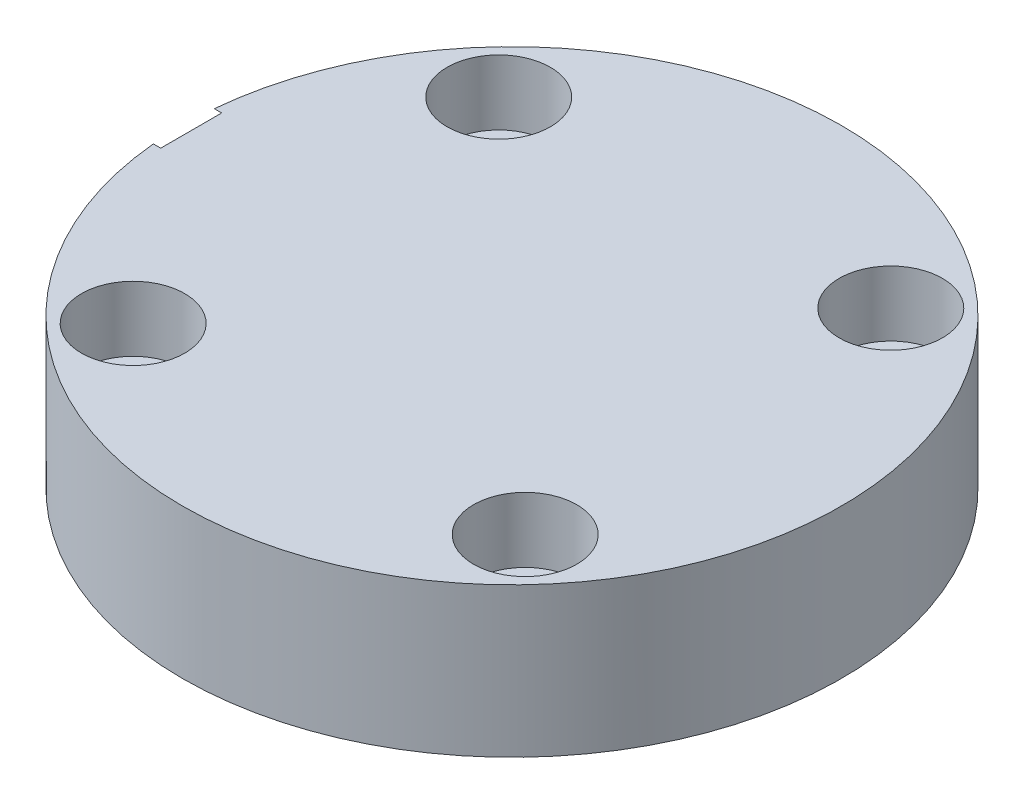
SolidWorks part; units mm, degrees
material "6061-T6 (SS)"
ref_plane "Front Plane" through (0, 0, 0) normal (0, 0, 1) x (1, 0, 0)
ref_plane "Top Plane" through (0, 0, 0) normal (0, 1, 0) x (1, 0, 0)
ref_plane "Right Plane" through (0, 0, 0) normal (1, 0, 0) x (0, 0, -1)
sketch "Sketch1" plane through (0, 0, 0) normal (0, 0, 1) x (1, 0, 0)
  line L0 (0, 8.636) -> (19.05, 8.636)
  line L1 (19.05, 8.636) -> (19.05, 0)
  line L2 (19.05, 0) -> (0, 0)
  line L3 (0, 0) -> (0, 8.636)
  line L4 (0, 0) -> (0, 8.636) construction
revolve "Revolve1" add sketch "Sketch1" angle 360 about L4 reverse direction yes
ref_plane "Plane1" through (0, 0, 0) normal (0, 0, 1) x (1, 0, 0)
sketch "Sketch2" plane through (0, 0, 0) normal (0, 0, 1) x (1, 0, 0)
  line L0 (-19.05, 5.08) -> (-19.05, 9.0488)
  line L1 (-19.05, 9.0488) -> (-18.542, 9.0488)
  line L2 (-18.542, 9.0488) -> (-18.542, 7.493)
  line L3 (-18.542, 7.493) -> (-18.1127, 7.0637)
  line L4 (-18.1127, 7.0637) -> (-7.874, 7.0637)
  line L5 (-7.874, 7.0637) -> (-6.7287, 5.08)
  line L6 (-6.7287, 5.08) -> (-19.05, 5.08)
  line L7 (-6.7287, 5.08) -> (-19.05, 5.08) construction
revolve "Cut-Revolve1" cut sketch "Sketch2" angle 360 about L7 reverse direction yes
cosmetic thread "Cosmetic Thread1" parameters "D1"=3.2004, "D2"=4.826
ref_plane "Plane2" through (0, 34.036, 0) normal (0, 1, 0) x (1, 0, 0)
ref_plane "Plane3" through (0, 0, 0) normal (0.7314, 0, 0.682) x (0.682, 0, -0.7314)
hole_wizard "Hole1" positions "Sketch4" profile "Sketch3" legacy
sketch "Sketch4" plane through (0, 8.636, 0) normal (0, 1, 0) x (1, 0, 0)
  point P0 (-10.5669, -11.3316)
sketch "Sketch3" plane through (-10.5669, 8.636, 11.3316) normal (1, 0, 0) x (0, 0, 1)
  line L0 (0, 0) -> (0, 8.636)
  line L1 (0, 8.636) -> (1.9812, 8.636)
  line L2 (1.9812, 8.636) -> (1.9812, 3.7592)
  line L3 (1.9812, 3.7592) -> (2.9845, 3.7592)
  line L4 (2.9845, 3.7592) -> (2.9845, 0)
  line L5 (2.9845, 0) -> (0, 0)
  line L6 (0, 110) -> (0, -10) construction
  dimension "Diameter" = 3.9624
  dimension "Depth" = 8.636
  dimension "C-Bore Diameter" = 5.969
  dimension "C-Bore Depth" = 3.7592
ref_plane "Plane4" through (0, 0, 0) normal (-0.682, 0, 0.7314) x (0.7314, 0, 0.682)
hole_wizard "Hole2" positions "Sketch6" profile "Sketch5" legacy
sketch "Sketch6" plane through (0, 8.636, 0) normal (0, 1, 0) x (1, 0, 0)
  point P0 (11.3316, -10.5669)
sketch "Sketch5" plane through (11.3316, 8.636, 10.5669) normal (1, 0, 0) x (0, 0, 1)
  line L0 (0, 0) -> (0, 8.636)
  line L1 (0, 8.636) -> (1.9812, 8.636)
  line L2 (1.9812, 8.636) -> (1.9812, 3.7592)
  line L3 (1.9812, 3.7592) -> (2.9845, 3.7592)
  line L4 (2.9845, 3.7592) -> (2.9845, 0)
  line L5 (2.9845, 0) -> (0, 0)
  line L6 (0, 110) -> (0, -10) construction
  dimension "Diameter" = 3.9624
  dimension "Depth" = 8.636
  dimension "C-Bore Diameter" = 5.969
  dimension "C-Bore Depth" = 3.7592
ref_plane "Plane5" through (0, 0, 0) normal (-0.7314, 0, -0.682) x (-0.682, 0, 0.7314)
hole_wizard "Hole3" positions "Sketch8" profile "Sketch7" legacy
sketch "Sketch8" plane through (0, 8.636, 0) normal (0, 1, 0) x (1, 0, 0)
  point P0 (10.5669, 11.3316)
sketch "Sketch7" plane through (10.5669, 8.636, -11.3316) normal (1, 0, 0) x (0, 0, 1)
  line L0 (0, 0) -> (0, 8.636)
  line L1 (0, 8.636) -> (1.9812, 8.636)
  line L2 (1.9812, 8.636) -> (1.9812, 3.7592)
  line L3 (1.9812, 3.7592) -> (2.9845, 3.7592)
  line L4 (2.9845, 3.7592) -> (2.9845, 0)
  line L5 (2.9845, 0) -> (0, 0)
  line L6 (0, 110) -> (0, -10) construction
  dimension "Diameter" = 3.9624
  dimension "Depth" = 8.636
  dimension "C-Bore Diameter" = 5.969
  dimension "C-Bore Depth" = 3.7592
ref_plane "Plane6" through (0, 0, 0) normal (0.682, 0, -0.7314) x (-0.7314, 0, -0.682)
hole_wizard "Hole4" positions "Sketch10" profile "Sketch9" legacy
sketch "Sketch10" plane through (0, 8.636, 0) normal (0, 1, 0) x (1, 0, 0)
  point P0 (-11.3316, 10.5669)
sketch "Sketch9" plane through (-11.3316, 8.636, -10.5669) normal (1, 0, 0) x (0, 0, 1)
  line L0 (0, 0) -> (0, 8.636)
  line L1 (0, 8.636) -> (1.9812, 8.636)
  line L2 (1.9812, 8.636) -> (1.9812, 3.7592)
  line L3 (1.9812, 3.7592) -> (2.9845, 3.7592)
  line L4 (2.9845, 3.7592) -> (2.9845, 0)
  line L5 (2.9845, 0) -> (0, 0)
  line L6 (0, 110) -> (0, -10) construction
  dimension "Diameter" = 3.9624
  dimension "Depth" = 8.636
  dimension "C-Bore Diameter" = 5.969
  dimension "C-Bore Depth" = 3.7592
ref_plane "Plane7" through (0, 0, 0) normal (0.7314, 0, 0.682) x (0.682, 0, -0.7314)
hole_wizard "Hole5" positions "Sketch12" profile "Sketch11" legacy
sketch "Sketch12" plane through (0, 0, 0) normal (0, -1, 0) x (-1, 0, 0)
  point P0 (0, 0)
sketch "Sketch11" plane through (0, 0, 0) normal (1, 0, 0) x (0, 0, -1)
  line L0 (0, 0) -> (0, 4.318)
  line L1 (0, 4.318) -> (10.3124, 4.318)
  line L2 (10.3124, 4.318) -> (10.3124, 0)
  line L3 (10.3124, 0) -> (0, 0)
  line L4 (0, 110) -> (0, -10) construction
  dimension "Diameter" = 20.6248
  dimension "Depth" = 4.318
ref_plane "Plane8" through (0, 10.16, 0) normal (0, 1, 0) x (1, 0, 0)
ref_plane "Plane9" through (0, 8.636, 0) normal (0, 1, 0) x (1, 0, 0)
ref_plane "Plane10" through (0, 0, 0) normal (0, 1, 0) x (1, 0, 0)
ref_plane "Plane11" through (0, 8.636, 0) normal (0, 1, 0) x (1, 0, 0)
ref_plane "Plane12" through (0, 11.938, 0) normal (0, 1, 0) x (1, 0, 0)
ref_plane "Plane13" through (0, 4.318, 0) normal (0, 1, 0) x (1, 0, 0)
ref_plane "Plane14" through (0, 8.636, 0) normal (0, 1, 0) x (1, 0, 0)
ref_plane "Plane15" through (0, 8.636, 0) normal (0, 1, 0) x (1, 0, 0)
hole_wizard "Hole6" positions "Sketch14" profile "Sketch13" legacy
sketch "Sketch14" plane through (0, 0, 0) normal (0, -1, 0) x (-1, 0, 0)
  point P0 (14.9305, -4.1406)
sketch "Sketch13" plane through (-14.9305, 0, 4.1406) normal (1, 0, 0) x (0, 0, -1)
  line L0 (0, 0) -> (0, 4.318)
  line L1 (0, 4.318) -> (1.7272, 4.318)
  line L2 (1.7272, 4.318) -> (1.7272, 0)
  line L3 (1.7272, 0) -> (0, 0)
  line L4 (0, 110) -> (0, -10) construction
  dimension "Diameter" = 3.4544
  dimension "Depth" = 4.318
hole_wizard "Hole7" positions "Sketch16" profile "Sketch15" legacy
sketch "Sketch16" plane through (0, 0, 0) normal (0, -1, 0) x (-1, 0, 0)
  point P0 (-4.1406, -14.9305)
sketch "Sketch15" plane through (4.1406, 0, 14.9305) normal (1, 0, 0) x (0, 0, -1)
  line L0 (0, 0) -> (0, 4.318)
  line L1 (0, 4.318) -> (1.7272, 4.318)
  line L2 (1.7272, 4.318) -> (1.7272, 0)
  line L3 (1.7272, 0) -> (0, 0)
  line L4 (0, 110) -> (0, -10) construction
  dimension "Diameter" = 3.4544
  dimension "Depth" = 4.318
hole_wizard "Hole8" positions "Sketch18" profile "Sketch17" legacy
sketch "Sketch18" plane through (0, 0, 0) normal (0, -1, 0) x (-1, 0, 0)
  point P0 (-14.9305, 4.1406)
sketch "Sketch17" plane through (14.9305, 0, -4.1406) normal (1, 0, 0) x (0, 0, -1)
  line L0 (0, 0) -> (0, 4.318)
  line L1 (0, 4.318) -> (1.7272, 4.318)
  line L2 (1.7272, 4.318) -> (1.7272, 0)
  line L3 (1.7272, 0) -> (0, 0)
  line L4 (0, 110) -> (0, -10) construction
  dimension "Diameter" = 3.4544
  dimension "Depth" = 4.318
hole_wizard "Hole9" positions "Sketch20" profile "Sketch19" legacy
sketch "Sketch20" plane through (0, 0, 0) normal (0, -1, 0) x (-1, 0, 0)
  point P0 (4.1406, 14.9305)
sketch "Sketch19" plane through (-4.1406, 0, -14.9305) normal (1, 0, 0) x (0, 0, -1)
  line L0 (0, 0) -> (0, 4.318)
  line L1 (0, 4.318) -> (1.7272, 4.318)
  line L2 (1.7272, 4.318) -> (1.7272, 0)
  line L3 (1.7272, 0) -> (0, 0)
  line L4 (0, 110) -> (0, -10) construction
  dimension "Diameter" = 3.4544
  dimension "Depth" = 4.318
ref_plane "Plane16" through (0, 4.318, 0) normal (0, 1, 0) x (1, 0, 0)
ref_plane "Plane17" through (0, 4.318, 0) normal (0, 1, 0) x (1, 0, 0)
ref_plane "Plane18" through (0, 4.318, 0) normal (0, 1, 0) x (1, 0, 0)
ref_plane "Plane19" through (0, 4.318, 0) normal (0, 1, 0) x (1, 0, 0)
ref_plane "a1 XY" through (0, 8.636, 0) normal (0, 1, 0) x (1, 0, 0)
ref_plane "a1 XZ" through (0, 0, -19.05) normal (0, 0, 1) x (1, 0, 0)
ref_plane "a1 YZ" through (0, 0, 0) normal (1, 0, 0) x (0, 0, -1)
ref_axis "a1 X" through (-80.9, 8.636, -19.05) along (1, 0, 0)
ref_axis "a1 Y" through (0, 8.636, 50) along (0, 0, -1)
ref_axis "a1 Z" through (0, 50, -19.05) along (0, -1, 0)
sketch3d "a1"
  point P0 (0, 8.636, -19.05)
ref_plane "a2 XY" through (0, 8.636, 0) normal (0, 1, 0) x (1, 0, 0)
ref_plane "a2 XZ" through (0, 0, 19.05) normal (0, 0, 1) x (1, 0, 0)
ref_plane "a2 YZ" through (0, 0, 0) normal (1, 0, 0) x (0, 0, -1)
ref_axis "a2 X" through (-80.9, 8.636, 19.05) along (1, 0, 0)
ref_axis "a2 Y" through (0, 8.636, 50) along (0, 0, -1)
ref_axis "a2 Z" through (0, 50, 19.05) along (0, -1, 0)
sketch3d "a2"
  point P0 (0, 8.636, 19.05)
ref_plane "ar3 XY" through (0, 4.318, 0) normal (0, 1, 0) x (1, 0, 0)
ref_plane "ar3 XZ" through (0, 0, 4.1406) normal (0, 0, 1) x (1, 0, 0)
ref_plane "ar3 YZ" through (-14.9305, 0, 0) normal (1, 0, 0) x (0, 0, -1)
ref_axis "ar3 X" through (-80.9, 4.318, 4.1406) along (1, 0, 0)
ref_axis "ar3 Y" through (-14.9305, 4.318, 50) along (0, 0, -1)
ref_axis "ar3 Z" through (-14.9305, 50, 4.1406) along (0, -1, 0)
sketch3d "ar3"
  point P0 (-14.9305, 4.318, 4.1406)
ref_plane "ar4 XY" through (0, 4.318, 0) normal (0, 1, 0) x (1, 0, 0)
ref_plane "ar4 XZ" through (0, 0, 14.9305) normal (0, 0, 1) x (1, 0, 0)
ref_plane "ar4 YZ" through (4.1406, 0, 0) normal (1, 0, 0) x (0, 0, -1)
ref_axis "ar4 X" through (-80.9, 4.318, 14.9305) along (1, 0, 0)
ref_axis "ar4 Y" through (4.1406, 4.318, 50) along (0, 0, -1)
ref_axis "ar4 Z" through (4.1406, 50, 14.9305) along (0, -1, 0)
sketch3d "ar4"
  point P0 (4.1406, 4.318, 14.9305)
ref_plane "ar5 XY" through (0, 4.318, 0) normal (0, 1, 0) x (1, 0, 0)
ref_plane "ar5 XZ" through (0, 0, -4.1406) normal (0, 0, 1) x (1, 0, 0)
ref_plane "ar5 YZ" through (14.9305, 0, 0) normal (1, 0, 0) x (0, 0, -1)
ref_axis "ar5 X" through (-80.9, 4.318, -4.1406) along (1, 0, 0)
ref_axis "ar5 Y" through (14.9305, 4.318, 50) along (0, 0, -1)
ref_axis "ar5 Z" through (14.9305, 50, -4.1406) along (0, -1, 0)
sketch3d "ar5"
  point P0 (14.9305, 4.318, -4.1406)
ref_plane "ar6 XY" through (0, 4.318, 0) normal (0, 1, 0) x (1, 0, 0)
ref_plane "ar6 XZ" through (0, 0, -14.9305) normal (0, 0, 1) x (1, 0, 0)
ref_plane "ar6 YZ" through (-4.1406, 0, 0) normal (1, 0, 0) x (0, 0, -1)
ref_axis "ar6 X" through (-80.9, 4.318, -14.9305) along (1, 0, 0)
ref_axis "ar6 Y" through (-4.1406, 4.318, 50) along (0, 0, -1)
ref_axis "ar6 Z" through (-4.1406, 50, -14.9305) along (0, -1, 0)
sketch3d "ar6"
  point P0 (-4.1406, 4.318, -14.9305)
ref_plane "b1 XY" through (0, 8.636, 0) normal (0, 1, 0) x (1, 0, 0)
ref_plane "b1 XZ" through (0, 0, 0) normal (0, 0, 1) x (1, 0, 0)
ref_plane "b1 YZ" through (0, 0, 0) normal (1, 0, 0) x (0, 0, -1)
ref_axis "b1 X" through (-80.9, 8.636, 0) along (1, 0, 0)
ref_axis "b1 Y" through (0, 8.636, 50) along (0, 0, -1)
ref_axis "b1 Z" through (0, 50, 0) along (0, -1, 0)
sketch3d "b1"
  point P0 (0, 8.636, 0)
ref_plane "c11 XY" through (0, 8.636, 0) normal (0, 1, 0) x (1, 0, 0)
ref_plane "c11 XZ" through (0, 0, 10.5669) normal (0, 0, 1) x (1, 0, 0)
ref_plane "c11 YZ" through (11.3316, 0, 0) normal (1, 0, 0) x (0, 0, -1)
ref_axis "c11 X" through (-80.9, 8.636, 10.5669) along (1, 0, 0)
ref_axis "c11 Y" through (11.3316, 8.636, 50) along (0, 0, -1)
ref_axis "c11 Z" through (11.3316, 50, 10.5669) along (0, -1, 0)
sketch3d "c11"
  point P0 (11.3316, 8.636, 10.5669)
ref_plane "c22 XY" through (0, 8.636, 0) normal (0, 1, 0) x (1, 0, 0)
ref_plane "c22 XZ" through (0, 0, -10.5669) normal (0, 0, 1) x (1, 0, 0)
ref_plane "c22 YZ" through (-11.3316, 0, 0) normal (1, 0, 0) x (0, 0, -1)
ref_axis "c22 X" through (-80.9, 8.636, -10.5669) along (1, 0, 0)
ref_axis "c22 Y" through (-11.3316, 8.636, 50) along (0, 0, -1)
ref_axis "c22 Z" through (-11.3316, 50, -10.5669) along (0, -1, 0)
sketch3d "c22"
  point P0 (-11.3316, 8.636, -10.5669)
ref_plane "d11 XY" through (0, 8.636, 0) normal (0, 1, 0) x (1, 0, 0)
ref_plane "d11 XZ" through (0, 0, -9.1179) normal (0, 0, 1) x (1, 0, 0)
ref_plane "d11 YZ" through (-12.6828, 0, 0) normal (1, 0, 0) x (0, 0, -1)
ref_axis "d11 X" through (-80.9, 8.636, -9.1179) along (1, 0, 0)
ref_axis "d11 Y" through (-12.6828, 8.636, 50) along (0, 0, -1)
ref_axis "d11 Z" through (-12.6828, 50, -9.1179) along (0, -1, 0)
sketch3d "d11"
  point P0 (-12.6828, 8.636, -9.1179)
ref_plane "d22 XY" through (0, 8.636, 0) normal (0, 1, 0) x (1, 0, 0)
ref_plane "d22 XZ" through (0, 0, -12.0158) normal (0, 0, 1) x (1, 0, 0)
ref_plane "d22 YZ" through (-9.9804, 0, 0) normal (1, 0, 0) x (0, 0, -1)
ref_axis "d22 X" through (-80.9, 8.636, -12.0158) along (1, 0, 0)
ref_axis "d22 Y" through (-9.9804, 8.636, 50) along (0, 0, -1)
ref_axis "d22 Z" through (-9.9804, 50, -12.0158) along (0, -1, 0)
sketch3d "d22"
  point P0 (-9.9804, 8.636, -12.0158)
ref_plane "j XY" through (0, 0, 0) normal (0, 1, 0) x (1, 0, 0)
ref_plane "j XZ" through (0, 0, 0) normal (0, 0, 1) x (1, 0, 0)
ref_plane "j YZ" through (0, 0, 0) normal (1, 0, 0) x (0, 0, -1)
ref_axis "j X" through (-80.9, 0, 0) along (1, 0, 0)
ref_axis "j Y" through (0, 0, 50) along (0, 0, -1)
ref_axis "j Z" through (0, 50, 0) along (0, -1, 0)
sketch3d "j"
  point P0 (0, 0, 0)
ref_plane "k1 XY" through (0, 0, 0) normal (0, 0, 1) x (1, 0, 0)
ref_plane "k1 XZ" through (0, 5.08, 0) normal (0, -1, 0) x (-1, 0, 0)
ref_plane "k1 YZ" through (-19.05, 0, 0) normal (1, 0, 0) x (0, 0, -1)
ref_axis "k1 X" through (-80.9, 5.08, 0) along (1, 0, 0)
ref_axis "k1 Y" through (-19.05, -50, 0) along (0, 1, 0)
ref_axis "k1 Z" through (-19.05, 5.08, 80.9) along (0, 0, -1)
sketch3d "k1"
  point P0 (-19.05, 5.08, 0)
ref_plane "k2 XY" through (0, 0, 0) normal (0, 0, 1) x (1, 0, 0)
ref_plane "k2 XZ" through (0, 8.636, 0) normal (0, -1, 0) x (-1, 0, 0)
ref_plane "k2 YZ" through (-19.05, 0, 0) normal (1, 0, 0) x (0, 0, -1)
ref_axis "k2 X" through (-80.9, 8.636, 0) along (1, 0, 0)
ref_axis "k2 Y" through (-19.05, -50, 0) along (0, 1, 0)
ref_axis "k2 Z" through (-19.05, 8.636, 80.9) along (0, 0, -1)
sketch3d "k2"
  point P0 (-19.05, 8.636, 0)
ref_plane "l1 XY" through (0, 0, 0) normal (0, 0, 1) x (1, 0, 0)
ref_plane "l1 XZ" through (0, 7.493, 0) normal (0, -1, 0) x (-1, 0, 0)
ref_plane "l1 YZ" through (-19.05, 0, 0) normal (1, 0, 0) x (0, 0, -1)
ref_axis "l1 X" through (-80.9, 7.493, 0) along (1, 0, 0)
ref_axis "l1 Y" through (-19.05, -50, 0) along (0, 1, 0)
ref_axis "l1 Z" through (-19.05, 7.493, 80.9) along (0, 0, -1)
sketch3d "l1"
  point P0 (-19.05, 7.493, 0)
ref_plane "l2 XY" through (0, 0, 0) normal (0, 0, 1) x (1, 0, 0)
ref_plane "l2 XZ" through (0, 2.667, 0) normal (0, -1, 0) x (-1, 0, 0)
ref_plane "l2 YZ" through (-19.05, 0, 0) normal (1, 0, 0) x (0, 0, -1)
ref_axis "l2 X" through (-80.9, 2.667, 0) along (1, 0, 0)
ref_axis "l2 Y" through (-19.05, -50, 0) along (0, 1, 0)
ref_axis "l2 Z" through (-19.05, 2.667, 80.9) along (0, 0, -1)
sketch3d "l2"
  point P0 (-19.05, 2.667, 0)
ref_plane "rg XY" through (0, 8.636, 0) normal (0, 1, 0) x (1, 0, 0)
ref_plane "rg XZ" through (0, 0, 0) normal (0, 0, 1) x (1, 0, 0)
ref_plane "rg YZ" through (0, 0, 0) normal (1, 0, 0) x (0, 0, -1)
ref_axis "rg X" through (-80.9, 8.636, 0) along (1, 0, 0)
ref_axis "rg Y" through (0, 8.636, 50) along (0, 0, -1)
ref_axis "rg Z" through (0, 50, 0) along (0, -1, 0)
sketch3d "rg"
  point P0 (0, 8.636, 0)
ref_plane "rh XY" through (0, 8.636, 0) normal (0, 1, 0) x (1, 0, 0)
ref_plane "rh XZ" through (0, 0, 0) normal (0, 0, 1) x (1, 0, 0)
ref_plane "rh YZ" through (0, 0, 0) normal (1, 0, 0) x (0, 0, -1)
ref_axis "rh X" through (-80.9, 8.636, 0) along (1, 0, 0)
ref_axis "rh Y" through (0, 8.636, 50) along (0, 0, -1)
ref_axis "rh Z" through (0, 50, 0) along (0, -1, 0)
sketch3d "rh"
  point P0 (0, 8.636, 0)
ref_plane "to dummy XY" through (0, 8.636, 0) normal (0, 1, 0) x (1, 0, 0)
ref_plane "to dummy XZ" through (0, 0, 0) normal (0, 0, 1) x (1, 0, 0)
ref_plane "to dummy YZ" through (0, 0, 0) normal (1, 0, 0) x (0, 0, -1)
ref_axis "to dummy X" through (-80.9, 8.636, 0) along (1, 0, 0)
ref_axis "to dummy Y" through (0, 8.636, 50) along (0, 0, -1)
ref_axis "to dummy Z" through (0, 50, 0) along (0, -1, 0)
sketch3d "to dummy"
  point P0 (0, 8.636, 0)
ref_plane "to nut XY" through (0, 10.16, 0) normal (0, 1, 0) x (1, 0, 0)
ref_plane "to nut XZ" through (0, 0, 0) normal (0, 0, 1) x (1, 0, 0)
ref_plane "to nut YZ" through (0, 0, 0) normal (1, 0, 0) x (0, 0, -1)
ref_axis "to nut X" through (-80.9, 10.16, 0) along (1, 0, 0)
ref_axis "to nut Y" through (0, 10.16, 50) along (0, 0, -1)
ref_axis "to nut Z" through (0, 50, 0) along (0, -1, 0)
sketch3d "to nut"
  point P0 (0, 10.16, 0)
ref_plane "to rod XY" through (0, 8.636, 0) normal (0, 1, 0) x (1, 0, 0)
ref_plane "to rod XZ" through (0, 0, 0) normal (0, 0, 1) x (1, 0, 0)
ref_plane "to rod YZ" through (0, 0, 0) normal (1, 0, 0) x (0, 0, -1)
ref_axis "to rod X" through (-80.9, 8.636, 0) along (1, 0, 0)
ref_axis "to rod Y" through (0, 8.636, 50) along (0, 0, -1)
ref_axis "to rod Z" through (0, 50, 0) along (0, -1, 0)
sketch3d "to rod"
  point P0 (0, 8.636, 0)
ref_plane "to tube XY" through (0, 4.318, 0) normal (0, 1, 0) x (1, 0, 0)
ref_plane "to tube XZ" through (0, 0, 0) normal (0, 0, 1) x (1, 0, 0)
ref_plane "to tube YZ" through (0, 0, 0) normal (1, 0, 0) x (0, 0, -1)
ref_axis "to tube X" through (-80.9, 4.318, 0) along (1, 0, 0)
ref_axis "to tube Y" through (0, 4.318, 50) along (0, 0, -1)
ref_axis "to tube Z" through (0, 50, 0) along (0, -1, 0)
sketch3d "to tube"
  point P0 (0, 4.318, 0)
ref_plane "to wiper XY" through (0, 8.636, 0) normal (0, 1, 0) x (1, 0, 0)
ref_plane "to wiper XZ" through (0, 0, 0) normal (0, 0, 1) x (1, 0, 0)
ref_plane "to wiper YZ" through (0, 0, 0) normal (1, 0, 0) x (0, 0, -1)
ref_axis "to wiper X" through (-80.9, 8.636, 0) along (1, 0, 0)
ref_axis "to wiper Y" through (0, 8.636, 50) along (0, 0, -1)
ref_axis "to wiper Z" through (0, 50, 0) along (0, -1, 0)
sketch3d "to wiper"
  point P0 (0, 8.636, 0)
ref_plane "to_rod XY" through (0, 11.938, 0) normal (0, 1, 0) x (1, 0, 0)
ref_plane "to_rod XZ" through (0, 0, 0) normal (0, 0, 1) x (1, 0, 0)
ref_plane "to_rod YZ" through (0, 0, 0) normal (1, 0, 0) x (0, 0, -1)
ref_axis "to_rod X" through (-80.9, 11.938, 0) along (1, 0, 0)
ref_axis "to_rod Y" through (0, 11.938, 50) along (0, 0, -1)
ref_axis "to_rod Z" through (0, 50, 0) along (0, -1, 0)
sketch3d "to_rod"
  point P0 (0, 11.938, 0)
ref_plane "track1 XY" through (0, 0, 0) normal (0, 1, 0) x (1, 0, 0)
ref_plane "track1 XZ" through (0, 0, 0) normal (0, 0, 1) x (1, 0, 0)
ref_plane "track1 YZ" through (-10.795, 0, 0) normal (1, 0, 0) x (0, 0, -1)
ref_axis "track1 X" through (-80.9, 0, 0) along (1, 0, 0)
ref_axis "track1 Y" through (-10.795, 0, 50) along (0, 0, -1)
ref_axis "track1 Z" through (-10.795, 50, 0) along (0, -1, 0)
sketch3d "track1"
  point P0 (-10.795, 0, 0)
ref_plane "track2 XY" through (0, 0, 0) normal (0, 1, 0) x (1, 0, 0)
ref_plane "track2 XZ" through (0, 0, -10.795) normal (0, 0, 1) x (1, 0, 0)
ref_plane "track2 YZ" through (0, 0, 0) normal (1, 0, 0) x (0, 0, -1)
ref_axis "track2 X" through (-80.9, 0, -10.795) along (1, 0, 0)
ref_axis "track2 Y" through (0, 0, 50) along (0, 0, -1)
ref_axis "track2 Z" through (0, 50, -10.795) along (0, -1, 0)
sketch3d "track2"
  point P0 (0, 0, -10.795)
ref_plane "track3 XY" through (0, 0, 0) normal (0, 1, 0) x (1, 0, 0)
ref_plane "track3 XZ" through (0, 0, 0) normal (0, 0, 1) x (1, 0, 0)
ref_plane "track3 YZ" through (10.795, 0, 0) normal (1, 0, 0) x (0, 0, -1)
ref_axis "track3 X" through (-80.9, 0, 0) along (1, 0, 0)
ref_axis "track3 Y" through (10.795, 0, 50) along (0, 0, -1)
ref_axis "track3 Z" through (10.795, 50, 0) along (0, -1, 0)
sketch3d "track3"
  point P0 (10.795, 0, 0)
ref_plane "track4 XY" through (0, 0, 0) normal (0, 1, 0) x (1, 0, 0)
ref_plane "track4 XZ" through (0, 0, 10.795) normal (0, 0, 1) x (1, 0, 0)
ref_plane "track4 YZ" through (0, 0, 0) normal (1, 0, 0) x (0, 0, -1)
ref_axis "track4 X" through (-80.9, 0, 10.795) along (1, 0, 0)
ref_axis "track4 Y" through (0, 0, 50) along (0, 0, -1)
ref_axis "track4 Z" through (0, 50, 10.795) along (0, -1, 0)
sketch3d "track4"
  point P0 (0, 0, 10.795)
